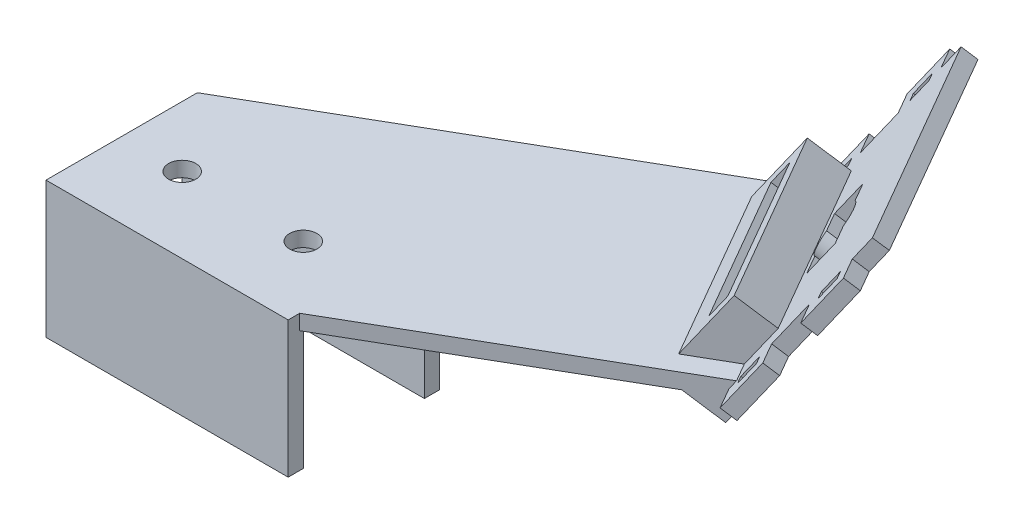
SolidWorks part; units mm, degrees
ref_plane "Front Plane" through (0, 0, 0) normal (0, 0, 1) x (1, 0, 0)
ref_plane "Top Plane" through (0, 0, 0) normal (0, 1, 0) x (1, 0, 0)
ref_plane "Right Plane" through (0, 0, 0) normal (1, 0, 0) x (0, 0, -1)
sketch "Sketch2" plane through (0, 0, 0) normal (1, 0, 0) x (0, 0, -1)
  line L0 (0, 0) -> (31.75, 0)
  line L1 (31.75, 0) -> (31.75, -28.575)
  line L2 (31.75, -28.575) -> (28.575, -28.575)
  line L3 (28.575, -28.575) -> (28.575, -3.175)
  line L4 (28.575, -3.175) -> (3.175, -3.175)
  line L5 (3.175, -3.175) -> (3.175, -28.575)
  line L6 (3.175, -28.575) -> (0, -28.575)
  line L7 (0, -28.575) -> (0, 0)
  dimension "D1" = 25.4
  dimension "D2" = 25.4
  dimension "D3" = 3.175
  dimension "D4" = 3.175
extrude "Boss-Extrude1" add sketch "Sketch2" along normal blind 50.8
sketch "Sketch3" plane through (0, 0, 0) normal (0, 1, 0) x (1, 0, 0)
  line L0 (0, 31.75) -> (0, 0) construction
  line L1 (50.8, 31.75) -> (50.8, 0) construction
  circle A0 centre (12.7, 15.875) radius 2.8575
  circle A1 centre (38.1, 15.875) radius 2.8575
  point P6 (0, 15.875)
  dimension "D1" = 5.715
  dimension "D2" = 12.7
  dimension "D3" = 12.7
extrude "Cut-Extrude1" cut sketch "Sketch3" against normal through all
sketch "Sketch4" plane through (0, 0, 0) normal (0, 1, 0) x (1, 0, 0)
  line L0 (0, 31.75) -> (76.2, 75.7441)
  line L1 (50.8, 31.75) -> (0, 31.75) construction
  line L2 (76.2, 75.7441) -> (101.6, 31.75)
  line L3 (101.6, 31.75) -> (50.8, 2.4206)
  line L4 (50.8, 31.75) -> (50.8, 0) construction
  line L5 (50.8, 31.75) -> (0, 31.75)
  line L6 (50.8, 31.75) -> (50.8, 2.4206)
  line L7 (50.8, 31.75) -> (101.6, 31.75) construction
  dimension "D1" = 30
  dimension "D2" = 50.8
extrude "Boss-Extrude2" add sketch "Sketch4" against normal blind 3.175
sketch "Sketch6" plane through (-13.7482, 0, -23.8125) normal (-0.5, 0, -0.866) x (-0.866, 0, 0.5)
  line L0 (-103.8632, -3.175) -> (-128.9944, 32.7161)
  line L1 (-128.9944, 32.7161) -> (-126.3936, 34.5373)
  line L2 (-126.3936, 34.5373) -> (-102.2104, 0)
  line L3 (-103.8632, 0) -> (-15.875, 0) construction
  line L4 (-102.2104, 0) -> (-103.8632, 0)
  line L5 (-103.8632, 0) -> (-103.8632, -3.175)
  dimension "D1" = 55
  dimension "D2" = 3.175
  dimension "D3" = 43.815
extrude "Boss-Extrude4" add sketch "Sketch6" against normal up to surface (50.8 mm away) up to face at (76.2, -1.5875, -17.0853)
sketch "Sketch7" plane through (61.648, -49.8443, -35.5925) normal (0.7094, -0.5736, -0.4096) x (-0.3185, 0.2575, -0.9123)
  line L0 (20.4499, 80.3342) -> (35.5201, 75.3437)
  line L1 (35.5201, 75.3437) -> (33.1246, 68.11)
  line L2 (33.1246, 68.11) -> (18.0544, 73.1005)
  line L3 (18.0544, 73.1005) -> (20.4499, 80.3342)
  line L4 (9.5619, 103.0038) -> (57.7865, 87.034) construction
  line L5 (2.675, 82.207) -> (19.2522, 76.7174) construction
  line L6 (9.5619, 103.0038) -> (-4.212, 61.4101) construction
  line L7 (33.6742, 95.0189) -> (27.985, 77.8389) construction
  line L8 (7.2138, 71.6736) -> (40.9709, 60.4948)
  line L9 (40.9709, 60.4948) -> (39.374, 55.6723)
  line L10 (39.374, 55.6723) -> (5.6168, 66.8512)
  line L11 (5.6168, 66.8512) -> (7.2138, 71.6736)
  line L12 (-4.212, 61.4101) -> (44.0125, 45.4404) construction
  line L13 (19.9003, 53.4253) -> (22.4954, 61.2617) construction
  dimension "D1" = 15.875
  dimension "D2" = 7.62
  dimension "D3" = 8.255
  dimension "D4" = 5.08
  dimension "D5" = 35.56
extrude "Cut-Extrude2" cut sketch "Sketch7" against normal up to next
sketch "Sketch8" plane through (61.648, -49.8443, -35.5925) normal (0.7094, -0.5736, -0.4096) x (-0.3185, 0.2575, -0.9123)
  line L0 (-4.212, 61.4101) -> (44.0125, 45.4404) construction
  line L1 (57.7865, 87.034) -> (44.0125, 45.4404) construction
  line L2 (9.5619, 103.0038) -> (57.7865, 87.034) construction
  line L3 (9.5619, 103.0038) -> (-4.212, 61.4101) construction
  line L4 (-4.212, 61.4101) -> (44.0125, 45.4404)
  line L5 (57.7865, 87.034) -> (44.0125, 45.4404)
  line L6 (9.5619, 103.0038) -> (57.7865, 87.034)
  line L7 (9.5619, 103.0038) -> (-4.212, 61.4101)
  line L8 (11.5779, 98.9917) -> (-0.1998, 63.4261)
  line L9 (-0.1998, 63.4261) -> (41.9966, 49.4525)
  line L10 (53.7743, 85.0181) -> (41.9966, 49.4525)
  line L11 (11.5779, 98.9917) -> (53.7743, 85.0181)
  dimension "D1" = 3.175
extrude "Boss-Extrude5" add sketch "Sketch8" along normal blind 8.255
sketch "Sketch9" plane through (67.5042, -54.5791, -38.9736) normal (0.7094, -0.5736, -0.4096) x (-0.3185, 0.2575, -0.9123)
  line L0 (0.0077, 60.0128) -> (39.7929, 46.8377)
  line L1 (0.0077, 60.0128) -> (-0.7908, 57.6016)
  line L2 (39.7929, 46.8377) -> (38.9944, 44.4265)
  line L3 (-0.7908, 57.6016) -> (38.9944, 44.4265)
  line L4 (-4.212, 61.4101) -> (44.0125, 45.4404) construction
  line L5 (-4.212, 61.4101) -> (44.0125, 45.4404) construction
  line L6 (20.8984, 56.4393) -> (19.9003, 53.4253) construction
  line L7 (-0.1998, 63.4261) -> (41.9966, 49.4525) construction
  line L8 (7.2138, 71.6736) -> (5.6168, 66.8512) construction
  dimension "D1" = 2.54
  dimension "D2" = 3.175
extrude "Boss-Extrude6" add sketch "Sketch9" against normal up to surface (8.255 mm away) up to face at (12.7, -3.175, -13.0175)
sketch "Sketch10" plane through (67.5042, -54.5791, -38.9736) normal (0.7094, -0.5736, -0.4096) x (-0.3185, 0.2575, -0.9123)
  line L0 (4.0198, 62.0287) -> (37.777, 50.8499)
  line L1 (4.0198, 62.0287) -> (3.2213, 59.6175)
  line L2 (37.777, 50.8499) -> (36.9785, 48.4386)
  line L3 (3.2213, 59.6175) -> (36.9785, 48.4386)
  line L4 (-0.1998, 63.4261) -> (41.9966, 49.4525) construction
  line L5 (7.2138, 71.6736) -> (5.6168, 66.8512) construction
  line L6 (39.374, 55.6723) -> (40.9709, 60.4948) construction
  line L7 (-0.7908, 57.6016) -> (38.9944, 44.4265) construction
  dimension "D1" = 3.175
extrude "Cut-Extrude3" cut sketch "Sketch10" against normal up to surface (8.255 mm away) up to face at (99.7822, 14.7706, -60.0299)
ref_point "Point2"
sketch "Sketch14" plane through (67.5042, -54.5791, -38.9736) normal (0.7094, -0.5736, -0.4096) x (-0.3185, 0.2575, -0.9123)
  line L0 (-2.5152, 66.534) -> (-7.3377, 68.131)
  line L1 (9.5619, 103.0038) -> (-4.212, 61.4101) construction
  line L2 (-7.3377, 68.131) -> (-3.7445, 78.9815)
  line L3 (-3.7445, 78.9815) -> (1.078, 77.3845)
  line L4 (1.078, 77.3845) -> (0.0799, 74.3705)
  line L5 (0.0799, 74.3705) -> (-1.7285, 74.9694)
  line L6 (-1.7285, 74.9694) -> (-3.3255, 70.1469)
  line L7 (-3.3255, 70.1469) -> (-1.5171, 69.548)
  line L8 (-1.5171, 69.548) -> (-2.5152, 66.534)
  line L9 (-4.212, 61.4101) -> (0.0077, 60.0128) construction
  line L10 (2.675, 82.207) -> (50.8995, 66.2372) construction
  line L11 (44.0125, 45.4404) -> (57.7865, 87.034) construction
  line L12 (33.6742, 95.0189) -> (19.1018, 51.014) construction
  line L13 (57.7865, 87.034) -> (9.5619, 103.0038) construction
  line L14 (-0.7908, 57.6016) -> (38.9944, 44.4265) construction
  line L15 (5.0586, 95.4648) -> (6.867, 94.8659)
  line L16 (3.4616, 90.6423) -> (5.0586, 95.4648)
  line L17 (5.2701, 90.0435) -> (3.4616, 90.6423)
  line L18 (4.2719, 87.0294) -> (5.2701, 90.0435)
  line L19 (-0.5505, 88.6264) -> (4.2719, 87.0294)
  line L20 (3.0427, 99.4769) -> (-0.5505, 88.6264)
  line L21 (7.8651, 97.88) -> (3.0427, 99.4769)
  line L22 (6.867, 94.8659) -> (7.8651, 97.88)
  line L23 (55.303, 73.4748) -> (56.9, 78.2973)
  line L24 (53.4946, 74.0737) -> (55.303, 73.4748)
  line L25 (52.4965, 71.0597) -> (53.4946, 74.0737)
  line L26 (57.3189, 69.4627) -> (52.4965, 71.0597)
  line L27 (60.9121, 80.3132) -> (57.3189, 69.4627)
  line L28 (56.0897, 81.9102) -> (60.9121, 80.3132)
  line L29 (55.0916, 78.8961) -> (56.0897, 81.9102)
  line L30 (56.9, 78.2973) -> (55.0916, 78.8961)
  line L31 (48.5159, 52.9794) -> (46.7074, 53.5783)
  line L32 (50.1128, 57.8018) -> (48.5159, 52.9794)
  line L33 (48.3044, 58.4007) -> (50.1128, 57.8018)
  line L34 (49.3025, 61.4147) -> (48.3044, 58.4007)
  line L35 (54.125, 59.8178) -> (49.3025, 61.4147)
  line L36 (50.5318, 48.9673) -> (54.125, 59.8178)
  line L37 (45.7093, 50.5642) -> (50.5318, 48.9673)
  line L38 (46.7074, 53.5783) -> (45.7093, 50.5642)
  dimension "D1" = 5.3975
  dimension "D2" = 3.175
  dimension "D3" = 3.175
  dimension "D4" = 5.08
  dimension "D5" = 1.905
extrude "Boss-Extrude10" add sketch "Sketch14" against normal blind 3.175
sketch "Sketch15" plane through (61.648, -49.8443, -35.5925) normal (0.7094, -0.5736, -0.4096) x (-0.3185, 0.2575, -0.9123)
  line L0 (4.0198, 62.0287) -> (7.2138, 71.6736)
  line L1 (7.2138, 71.6736) -> (40.9709, 60.4948)
  line L2 (40.9709, 60.4948) -> (37.777, 50.8499)
  line L3 (37.777, 50.8499) -> (41.9966, 49.4525)
  line L4 (41.9966, 49.4525) -> (53.7743, 85.0181)
  line L5 (53.7743, 85.0181) -> (11.5779, 98.9917)
  line L6 (11.5779, 98.9917) -> (-0.1998, 63.4261)
  line L7 (-0.1998, 63.4261) -> (4.0198, 62.0287)
  line L8 (20.4499, 80.3342) -> (35.5201, 75.3437)
  line L9 (35.5201, 75.3437) -> (33.1246, 68.11)
  line L10 (33.1246, 68.11) -> (18.0544, 73.1005)
  line L11 (18.0544, 73.1005) -> (20.4499, 80.3342)
extrude "Boss-Extrude11" add sketch "Sketch15" along normal up to surface (8.255 mm away) up to face at (87.0998, 1.193, -83.137)
sketch "Sketch16" plane through (67.5042, -54.5791, -38.9736) normal (0.7094, -0.5736, -0.4096) x (-0.3185, 0.2575, -0.9123)
  line L0 (9.5619, 103.0038) -> (-3.2139, 64.4242)
  line L1 (-2.5152, 66.534) -> (-4.212, 61.4101) construction
  line L2 (-3.2139, 64.4242) -> (1.0058, 63.0268)
  line L3 (1.0058, 63.0268) -> (5.1978, 75.6858)
  line L4 (5.1978, 75.6858) -> (44.9831, 62.5107)
  line L5 (44.9831, 62.5107) -> (40.791, 49.8518)
  line L6 (40.791, 49.8518) -> (45.0107, 48.4544)
  line L7 (44.0125, 45.4404) -> (45.7093, 50.5642) construction
  line L8 (45.0107, 48.4544) -> (57.7865, 87.034)
  line L9 (57.7865, 87.034) -> (9.5619, 103.0038)
  line L10 (-4.212, 61.4101) -> (0.0077, 60.0128) construction
  line L12 (0.0077, 60.0128) -> (-0.7908, 57.6016) construction
  line L13 (38.9944, 44.4265) -> (39.7929, 46.8377) construction
  line L14 (7.2138, 71.6736) -> (40.9709, 60.4948) construction
  dimension "D1" = 3.175
  dimension "D2" = 3.175
extrude "Cut-Extrude4" cut sketch "Sketch16" along normal up to surface (-3.175 mm away) from surface up to face at (95.175, 20.6996, -88.7157) starting at face at (97.5298, 16.5917, -58.7295)
sketch "Sketch17" plane through (11.6518, 0, 20.1816) normal (0.5, 0, 0.866) x (0.866, 0, -0.5)
  line L0 (117.4942, 7.4354) -> (109.8456, -3.488) construction
  line L1 (109.8456, -3.488) -> (103.0835, 1.2469) construction
  line L2 (102.2104, 0) -> (103.0835, 1.2469) construction
  line L3 (112.2879, 0) -> (109.8456, -3.488)
  line L4 (109.8456, -3.488) -> (103.0835, 1.2469)
  line L5 (102.2104, 0) -> (103.0835, 1.2469)
  line L6 (117.6763, 7.6955) -> (111.1204, -1.6674) construction
  line L7 (102.2104, 0) -> (112.2879, 0)
  line M1 (111.1204, -1.6674) -> (109.8456, -3.488)
  line M2 (109.8456, -3.488) -> (103.0835, 1.2469)
  line M3 (103.0835, 1.2469) -> (102.2104, 0)
extrude "Boss-Extrude12" add sketch "Sketch17" against normal up to surface (4.445 mm away) contours L7 L3 M2 M1 region at (106.048, -1.1627, -34.318) up to face at (104.9423, 4.3412, -38.8123)
extrude "Cut-Extrude5" cut sketch "Sketch17<3>" against normal up to surface (4.445 mm away) contours L7 L4 M3 region at (101.1868, 0.4156, -31.5114) up to face at (104.4257, 4.1705, -38.5141)
sketch "Sketch17<3>" plane through (11.6518, 0, 20.1816) normal (0.5, 0, 0.866) x (0.866, 0, -0.5) same geometry as "Sketch17"
extrude "Boss-Extrude13" add sketch "Sketch17<4>" along normal up to surface (-46.355 mm away) from surface contours L7 L3 M2 M1 region at (106.048, -1.1627, -34.318) up to face at (83.9873, 4.3412, -75.1074) starting at face at (97.1743, 19.789, -87.8536)
sketch "Sketch17<4>" plane through (11.6518, 0, 20.1816) normal (0.5, 0, 0.866) x (0.866, 0, -0.5) same geometry as "Sketch17"
extrude "Cut-Extrude6" cut sketch "Sketch17<5>" along normal up to surface (-46.355 mm away) from surface contours L7 L4 M3 region at (101.1868, 0.4156, -31.5114) up to face at (83.4707, 4.1705, -74.8092) starting at face at (97.1743, 19.789, -87.8536)
sketch "Sketch17<5>" plane through (11.6518, 0, 20.1816) normal (0.5, 0, 0.866) x (0.866, 0, -0.5) same geometry as "Sketch17"
sketch "Sketch18" plane through (65.2518, -52.758, -37.6731) normal (-0.7094, 0.5736, 0.4096) x (0.3185, -0.2575, 0.9123)
  line L0 (-27.985, 77.8389) -> (-25.5895, 70.6053) construction
  line L1 (-20.4499, 80.3342) -> (-35.5201, 75.3437) construction
  line L2 (-33.1246, 68.11) -> (-18.0544, 73.1005) construction
  line L3 (-34.3223, 71.7268) -> (-19.2522, 76.7174) construction
  line L4 (-35.5201, 75.3437) -> (-33.1246, 68.11) construction
  line L5 (-18.0544, 73.1005) -> (-20.4499, 80.3342) construction
  circle A0 centre (-26.7872, 74.2221) radius 5.08
  dimension "D1" = 10.16
extrude "Cut-Extrude7" cut sketch "Sketch18" against normal through all
